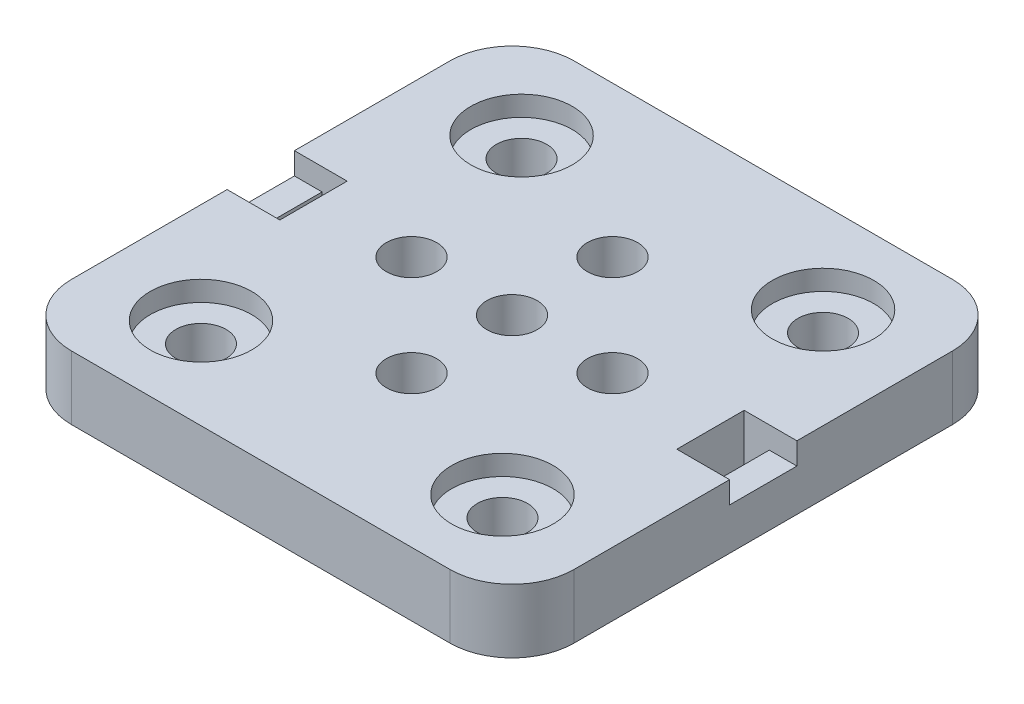
SolidWorks part; units mm, degrees
ref_plane "Front Plane" through (0, 0, 0) normal (0, 0, 1) x (1, 0, 0)
ref_plane "Top Plane" through (0, 0, 0) normal (0, 1, 0) x (1, 0, 0)
ref_plane "Right Plane" through (0, 0, 0) normal (1, 0, 0) x (0, 0, -1)
sketch "Sketch1" plane through (0, 0, 0) normal (0, 1, 0) x (1, 0, 0)
  line L0 (0, 25) -> (50, 25) construction
  line L1 (6.17, 0) -> (43.83, 0)
  line L2 (0, 6.17) -> (0, 43.83)
  line L3 (6.17, 50) -> (43.83, 50)
  line L4 (50, 6.17) -> (50, 43.83)
  line L5 (25, 35) -> (25, 25) construction
  line L6 (5.25, 21.65) -> (0, 21.65)
  line L7 (5.25, 21.65) -> (5.25, 28.35)
  line L8 (5.25, 28.35) -> (0, 28.35)
  line L9 (0, 21.65) -> (0, 28.35)
  line L10 (5.25, 21.65) -> (0, 28.35) construction
  line L11 (5.25, 28.35) -> (0, 21.65) construction
  line L12 (25, 25) -> (25, 15) construction
  line L13 (2.75, 28.35) -> (2.75, 21.65)
  line L14 (50, 21.65) -> (50, 28.35)
  line L15 (44.75, 28.35) -> (50, 21.65) construction
  line L16 (44.75, 21.65) -> (50, 28.35) construction
  line L17 (44.75, 21.65) -> (50, 21.65)
  line L18 (47.25, 28.35) -> (47.25, 21.65)
  line L19 (44.75, 21.65) -> (44.75, 28.35)
  line L20 (44.75, 28.35) -> (50, 28.35)
  circle A0 centre (10, 9.05) radius 5.05
  circle A1 centre (40, 9.05) radius 5.05
  circle A2 centre (10, 9.05) radius 2.5
  circle A3 centre (40, 9.05) radius 2.5
  circle A4 centre (25, 25) radius 2.51
  circle A5 centre (35, 25) radius 2.51
  circle A6 centre (15, 25) radius 2.51
  circle A7 centre (25, 35) radius 2.51
  circle A8 centre (25, 15) radius 2.51
  circle A9 centre (40, 40.95) radius 5.05
  circle A10 centre (40, 40.95) radius 2.5
  circle A11 centre (10, 40.95) radius 2.5
  circle A12 centre (10, 40.95) radius 5.05
  arc A13 (50, 43.83) -> (43.83, 50) centre (43.83, 43.83) ccw
  arc A14 (6.17, 50) -> (0, 43.83) centre (6.17, 43.83) ccw
  arc A15 (50, 6.17) -> (43.83, 0) centre (43.83, 6.17) cw
  arc A16 (0, 6.17) -> (6.17, 0) centre (6.17, 6.17) ccw
  point P13 (2.625, 25)
  point P46 (0, 50)
  point P49 (50, 0)
  point P52 (0, 0)
  dimension "D3" = 30
  dimension "D4" = 10.1
  dimension "D5" = 10
  dimension "D8" = 5
  dimension "D11" = 5.02
  dimension "D16" = 2.5
  dimension "D17" = 6.17
  dimension "D1" = 50
  dimension "D2" = 50
  dimension "D6" = 9.05
  dimension "D7" = 9.05
  dimension "D9" = 5.25
  dimension "D10" = 6.7
  dimension "D12" = 20
  dimension "D13" = 10
  dimension "D14" = 20
  dimension "D15" = 10
extrude "Boss-Extrude1" add sketch "Sketch1" against normal blind 6.35 contours L2 A16 L1 A15 L4 L17 L19 L20 A13 L3 A14 L8 L7 L6 A12 A9 A8 A7 A6 A5 A4 A1 A0 | A9 A10 | L20 L18 L17 L4 | A1 A3 | A0 A2 | A12 A11 | L13 L8 L2 L6 region at (2.3072, 0, -2.3072) region at (1.375, 0, -25) region at (48.625, 0, -25) region at (5.0928, 0, -9.05) region at (35.0928, 0, -9.05) region at (35.0928, 0, -40.95) region at (5.0928, 0, -40.95)
extrude "Cut-Extrude1" cut sketch "Sketch1<4>" against normal blind 2.18 contours L13 L8 L2 L6 | L20 L18 L17 L4 region at (1.375, 0, -25) region at (48.625, 0, -25)
sketch "Sketch1<4>" plane through (0, 0, 0) normal (0, 1, 0) x (1, 0, 0) same geometry as "Sketch1"
extrude "Cut-Extrude2" cut sketch "Sketch1<5>" against normal blind 2 contours A12 A11 | A9 A10 | A1 A3 | A0 A2 region at (5.0928, 0, -9.05) region at (35.0928, 0, -9.05) region at (35.0928, 0, -40.95) region at (5.0928, 0, -40.95)
sketch "Sketch1<5>" plane through (0, 0, 0) normal (0, 1, 0) x (1, 0, 0) same geometry as "Sketch1"
